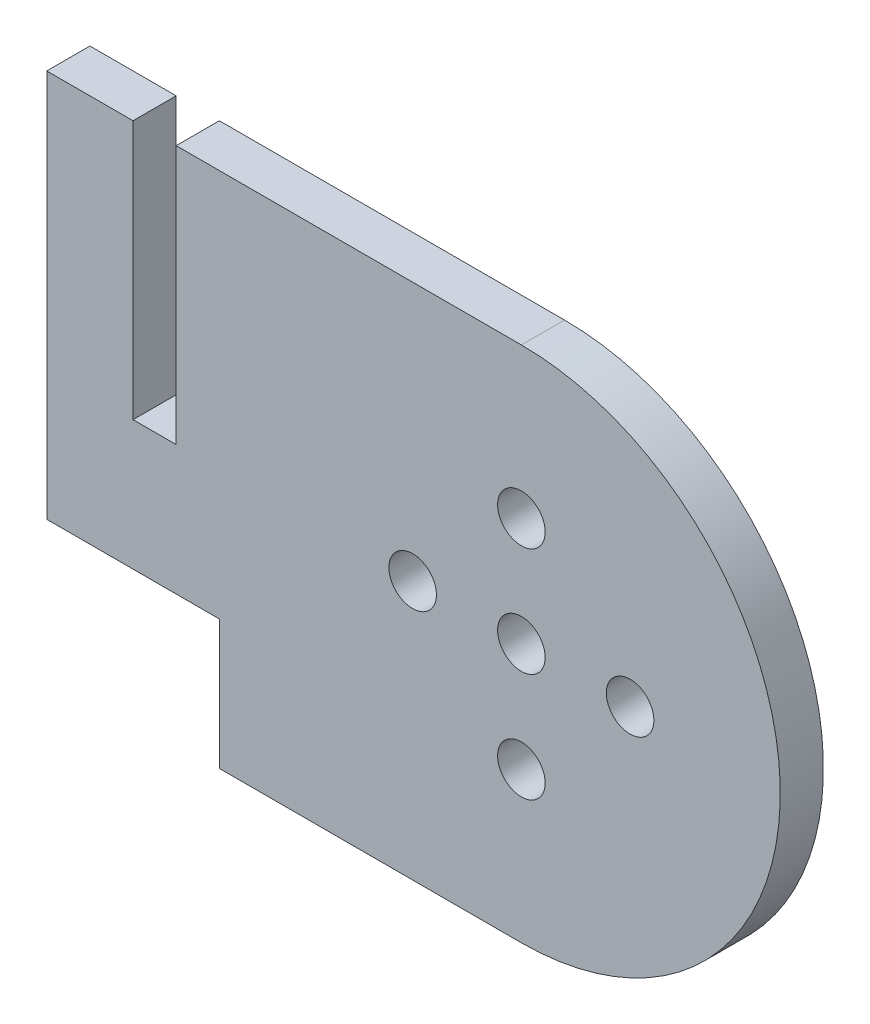
SolidWorks part; units mm, degrees
ref_plane "Front Plane" through (0, 0, 0) normal (0, 0, 1) x (1, 0, 0)
ref_plane "Top Plane" through (0, 0, 0) normal (0, 1, 0) x (1, 0, 0)
ref_plane "Right Plane" through (0, 0, 0) normal (1, 0, 0) x (0, 0, -1)
sketch "Sketch1" plane through (0, 0, 0) normal (0, 0, 1) x (1, 0, 0)
  line L0 (-6.2201, 19.05) -> (19.1799, 19.05)
  line L1 (-3.0451, -19.05) -> (19.1799, -19.05)
  line L2 (-15.7451, -9.525) -> (-15.7451, 19.05)
  line L3 (-15.7451, 19.05) -> (-9.3951, 19.05)
  line L5 (-3.0451, -9.525) -> (-15.7451, -9.525)
  line L6 (-15.7451, 19.05) -> (0, 0) construction
  line L7 (-3.0451, -9.525) -> (-3.0451, -19.05)
  line L8 (-9.3951, 19.05) -> (-9.3951, 0)
  line L9 (-9.3951, 0) -> (-6.2201, 0)
  line L10 (-6.2201, 19.05) -> (-6.2201, 0)
  arc A0 (19.1799, -19.05) -> (19.1799, 19.05) centre (19.1799, 0) ccw
  circle A1 centre (19.1799, 8) radius 1.75
  circle A2 centre (19.1799, 0) radius 1.75
  circle A3 centre (27.1799, 0) radius 1.75
  circle A4 centre (19.1799, -8) radius 1.75
  circle A5 centre (11.1799, 0) radius 1.75
  point P0 (0, 0)
  point P24 (19.1799, 0)
  dimension "D2" = 3.5
  dimension "D6" = 3.5
  dimension "D1" = 25.4
  dimension "D3" = 3.175
  dimension "D4" = 6.35
  dimension "D5" = 8
  dimension "D8" = 9.525
  dimension "D9" = 3.175
  dimension "D7" = 4
extrude "Boss-Extrude1" add sketch "Sketch1" along normal blind 3.175
